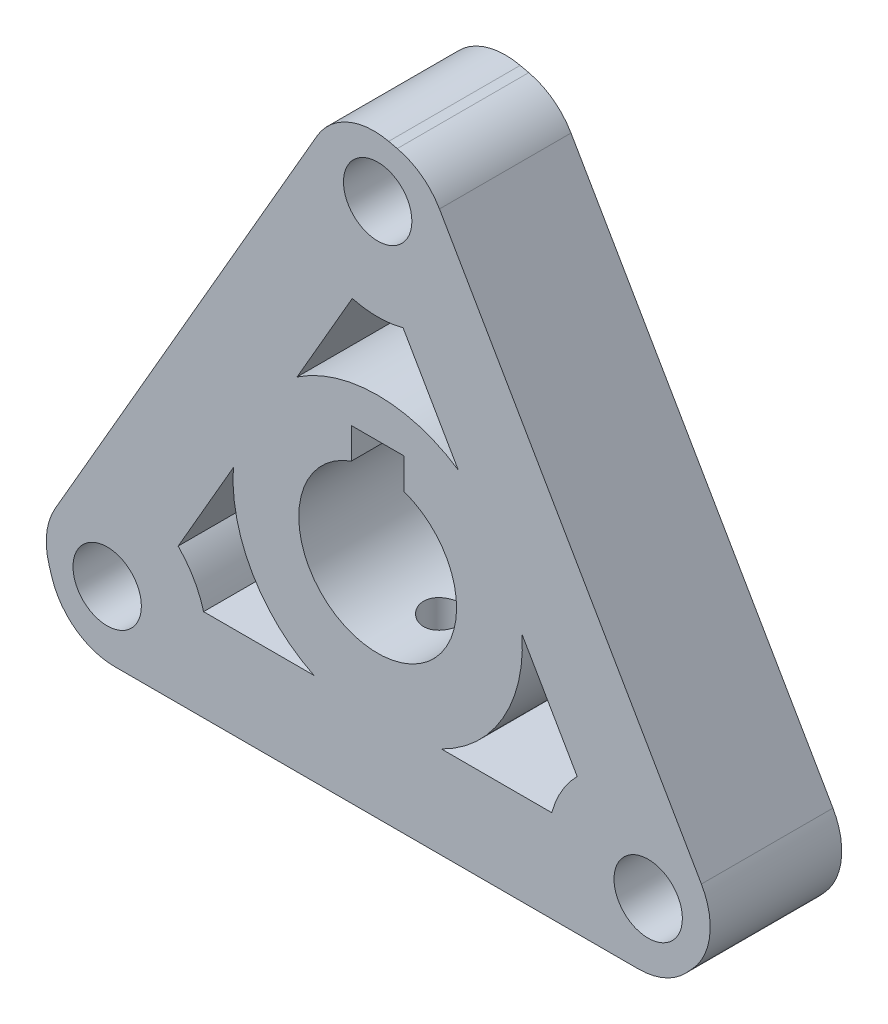
SolidWorks part; units mm, degrees
ref_plane "正面" through (0, 0, 0) normal (0, 0, 1) x (1, 0, 0)
ref_plane "平面" through (0, 0, 0) normal (0, 1, 0) x (1, 0, 0)
ref_plane "右側面" through (0, 0, 0) normal (1, 0, 0) x (0, 0, -1)
sketch "ｽｹｯﾁ1" plane through (0, 0, 0) normal (0, 0, 1) x (1, 0, 0)
  line L0 (0, 0) -> (-20.5681, -11.875) construction
  line L1 (0, 23.75) -> (-20.5681, -11.875) construction
  line L2 (-20.5681, -11.875) -> (20.5681, -11.875) construction
  line L3 (20.5681, -11.875) -> (0, 23.75) construction
  line L4 (-4.6132, 25.7596) -> (-24.5285, -8.7346)
  line L5 (-20.0019, -16.875) -> (19.8287, -16.875)
  line L6 (24.6151, -8.8846) -> (4.6999, 25.6096)
  line L7 (0, 33.75) -> (-29.2284, -16.875) construction
  line L8 (29.2284, -16.875) -> (0, 33.75) construction
  line L9 (1.4894, 27.9826) -> (0.8365, 28.1326)
  line L10 (-29.2284, -16.875) -> (29.2284, -16.875) construction
  line L11 (-24.9784, -12.7015) -> (-24.7818, -13.3419)
  line L12 (23.489, -15.2812) -> (23.9453, -14.7908)
  line L14 (-2, 4) -> (2, 4)
  line L15 (-2, 4) -> (-2, 8)
  line L16 (-2, 8) -> (2, 8)
  line L17 (2, 4) -> (2, 8)
  line L18 (-2, 4) -> (2, 8) construction
  line L19 (-2, 8) -> (2, 4) construction
  circle A0 centre (0, 0) radius 11.875 construction
  circle A1 centre (0, 23.75) radius 2.6
  circle A2 centre (20.5681, -11.875) radius 2.6
  circle A3 centre (-20.5681, -11.875) radius 2.6
  circle A4 centre (0, 0) radius 6
  arc A5 (-24.9784, -12.7015) -> (-24.5285, -8.7346) centre (-20.1984, -11.2346) cw
  arc A6 (-24.7818, -13.3419) -> (-20.0019, -16.875) centre (-20.0019, -11.875) ccw
  arc A7 (23.489, -15.2812) -> (19.8287, -16.875) centre (19.8287, -11.875) cw
  arc A8 (23.9453, -14.7908) -> (24.6151, -8.8846) centre (20.285, -11.3846) ccw
  arc A9 (1.4894, 27.9826) -> (4.6999, 25.6096) centre (0.3697, 23.1096) cw
  arc A10 (0.8365, 28.1326) -> (-4.6132, 25.7596) centre (-0.2831, 23.2596) ccw
  point P31 (0, 6)
  dimension "D1" = 5.2
  dimension "D2" = 5.2
  dimension "D3" = 5.2
  dimension "D5" = 12
  dimension "D7" = 5
  dimension "D4" = 23.75
  dimension "D8" = 4
  dimension "D9" = 4
  dimension "D6" = 5
extrude "ﾎﾞｽ - 押し出し1" add sketch "ｽｹｯﾁ1" along normal blind 10 contours L9 A10 L4 A5 L11 A6 L5 A7 L12 A8 L6 A9 A1 A2 A3 A4 L15 L16 L17 region at (-2.0089, 27.223, 0)
sketch "ｽｹｯﾁ3" plane through (0, -16.875, 0) normal (0, -1, 0) x (1, 0, 0)
  line L0 (-20.0019, 0) -> (19.8287, 0) construction
  circle A0 centre (0, 5) radius 1.5
  dimension "D1" = 5
  dimension "D2" = 3
extrude "ｶｯﾄ - 押し出し1" cut sketch "ｽｹｯﾁ3" against normal up to next
sketch "ｽｹｯﾁ4" plane through (0, -16.875, 0) normal (0, -1, 0) x (1, 0, 0)
  circle A0 centre (0, 5) radius 3.1
  dimension "D1" = 6.2
extrude "ｶｯﾄ - 押し出し2" cut sketch "ｽｹｯﾁ4" against normal blind 3
sketch "ｽｹｯﾁ5" plane through (0, 0, 0) normal (0, 0, -1) x (-1, 0, 0)
  line L12 (0, 19.75) -> (-17.104, -9.875)
  line L13 (-17.104, -9.875) -> (17.104, -9.875)
  line L14 (17.104, -9.875) -> (0, 19.75)
  line L15 (0, 19.75) -> (-17.104, -9.875)
  line L16 (-17.104, -9.875) -> (17.104, -9.875)
  line L17 (17.104, -9.875) -> (0, 19.75)
  circle A12 centre (0, 23.75) radius 7.6
  circle A13 centre (0, 23.75) radius 7.6
  circle A15 centre (-20.5681, -11.875) radius 7.6
  circle A16 centre (-20.5681, -11.875) radius 7.6
  circle A18 centre (20.5681, -11.875) radius 7.6
  circle A19 centre (20.5681, -11.875) radius 7.6
  circle A20 centre (0, 0) radius 11
  dimension "D4" = 22
  dimension "D1" = 5
  dimension "D2" = 5
  dimension "D3" = 5
  dimension "D5" = 7
extrude "ｶｯﾄ - 押し出し3" cut sketch "ｽｹｯﾁ5" against normal blind 10 contours A20 L15 A16 L16 | A20 L17 A13 L15 | A20 L16 A19 L17 region at (0, 12.8976, 0) region at (11.1697, -6.4488, 0) region at (-11.1697, -6.4488, 0)
